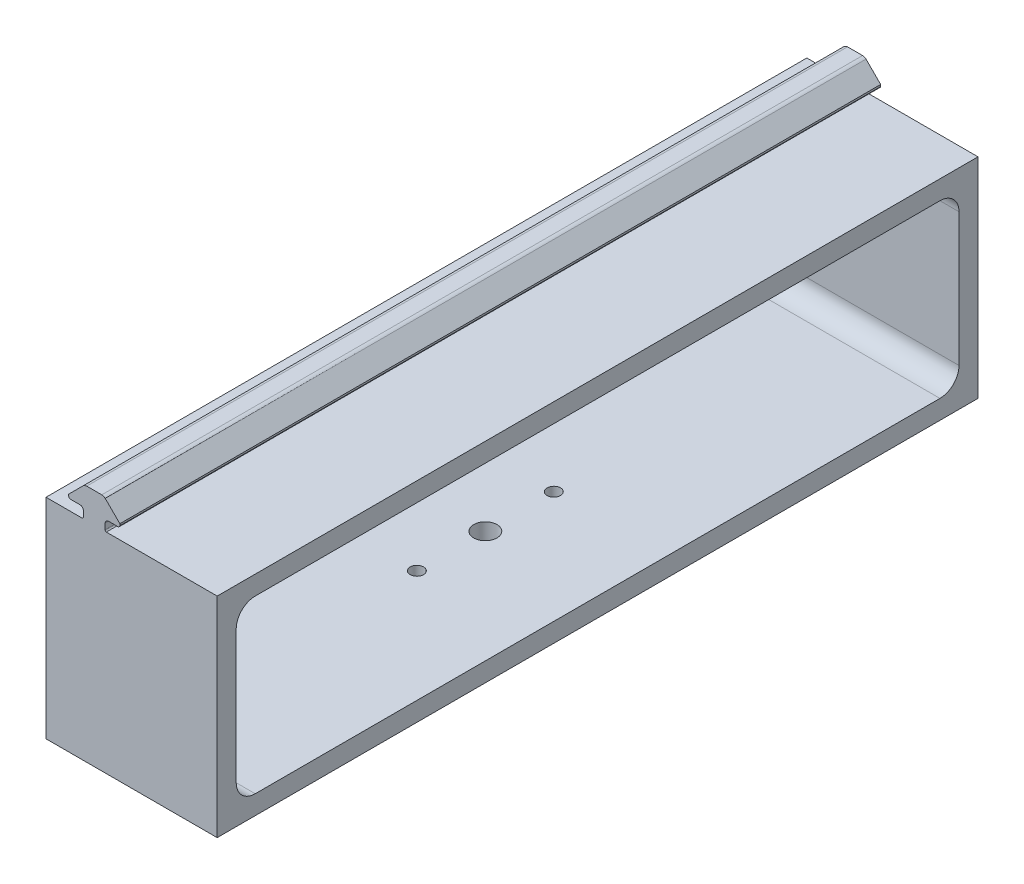
SolidWorks part; units mm, degrees
ref_plane "Front Plane" through (0, 0, 0) normal (0, 0, 1) x (1, 0, 0)
ref_plane "Top Plane" through (0, 0, 0) normal (0, 1, 0) x (1, 0, 0)
ref_plane "Right Plane" through (0, 0, 0) normal (1, 0, 0) x (0, 0, -1)
sketch "body sketch" plane through (0, 0, 0) normal (0, 0, 1) x (1, 0, 0)
  line L0 (-9.8141, 31.5907) -> (-9.8141, 23.3992) construction
  line L1 (-11.7928, 31.2966) -> (-7.8354, 31.2966)
  line L2 (-6.9378, 30.9425) -> (-3.0834, 27.088)
  line L3 (-3.0834, 27.088) -> (-3.0834, 26.6272)
  line L4 (-3.5442, 26.1664) -> (-6.0939, 26.1664)
  line L5 (-6.9378, 25.3225) -> (-6.9378, 23.7712)
  line L6 (-12.6904, 25.3225) -> (-12.6904, 23.7712)
  line L7 (-16.084, 26.1664) -> (-13.5343, 26.1664)
  line L8 (-16.5448, 27.088) -> (-16.5448, 26.6272)
  line L9 (-12.6904, 30.9425) -> (-16.5448, 27.088)
  line L10 (-12.9824, 23.4093) -> (-22.5, 23.4093)
  line L11 (-22.5, 23.4093) -> (-22.5, -31.5907)
  line L12 (-22.5, -31.5907) -> (22.5, -31.5907)
  line L13 (22.5, -31.5907) -> (22.5, 23.4093)
  line L14 (22.5, 23.4093) -> (-6.6458, 23.4093)
  arc A0 (-6.0939, 26.1664) -> (-6.9378, 25.3225) centre (-6.0704, 25.299) ccw
  arc A1 (-3.5442, 26.1664) -> (-3.0834, 26.6272) centre (-3.6789, 26.7619) ccw
  arc A2 (-6.9378, 23.7712) -> (-6.6458, 23.4093) centre (-6.5587, 23.7784) ccw
  arc A3 (-7.8354, 31.2966) -> (-6.9378, 30.9425) centre (-8.1959, 29.0683) cw
  arc A4 (-12.6904, 23.7712) -> (-12.9824, 23.4093) centre (-13.0695, 23.7784) cw
  arc A5 (-13.5343, 26.1664) -> (-12.6904, 25.3225) centre (-13.5578, 25.299) cw
  arc A6 (-16.084, 26.1664) -> (-16.5448, 26.6272) centre (-15.9493, 26.7619) cw
  arc A7 (-11.7928, 31.2966) -> (-12.6904, 30.9425) centre (-11.4323, 29.0683) ccw
  point P5 (-9.8141, 31.2966)
  point P32 (-9.8141, 31.2966)
extrude "Boss-Extrude1" add sketch "body sketch" along normal blind 200
sketch "body cut" plane through (22.5, 0, 0) normal (1, 0, 0) x (0, 0, -1)
  line L0 (-100, 23.4093) -> (-100, -31.5907) construction
  line L1 (-200, 23.4093) -> (0, 23.4093) construction
  line L2 (-200, -31.5907) -> (0, -31.5907) construction
  line L3 (-200, -4.0907) -> (0, -4.0907) construction
  line L4 (-200, -31.5907) -> (-200, 23.4093) construction
  line L5 (0, -31.5907) -> (0, 23.4093) construction
  line L7 (-195, -26.5907) -> (-5, -26.5907)
  line L8 (-195, -26.5907) -> (-195, 18.4093)
  line L9 (-195, 18.4093) -> (-5, 18.4093)
  line L10 (-5, -26.5907) -> (-5, 18.4093)
  line L11 (-195, -26.5907) -> (-5, 18.4093) construction
  line L12 (-195, 18.4093) -> (-5, -26.5907) construction
  point P12 (-100, -4.0907)
  dimension "D1" = 190
  dimension "D2" = 45
extrude "main body hole" cut sketch "body cut" against normal through all both and the other way through all
sketch "screw holes" plane through (0, -31.5907, 0) normal (0, -1, 0) x (-1, 0, 0)
  line L0 (-23.3392, -100) -> (13.9588, -100) construction
  line L1 (22.5, -100) -> (-38.9995, -100) construction
  line L2 (22.5, -200) -> (22.5, 0) construction
  line L3 (-22.5, -200) -> (-22.5, 0) construction
  line L4 (22.5, 0) -> (-22.5, 0) construction
  circle A0 centre (7.01, -100) radius 3.0578
  circle A1 centre (7.01, -81.9999) radius 1.7645
  circle A2 centre (7.01, -117.9999) radius 1.7645
  dimension "D8" = 3.529
  dimension "D9" = 6.1156
  dimension "D10" = 3.529
  dimension "D1" = 18.0001
  dimension "D2" = 17.9999
  dimension "D3" = 0
  dimension "D4" = 15.49
  dimension "D5" = 0
  dimension "D6" = 15.49
  dimension "D7" = 15.49
extrude "hole cuts" cut sketch "screw holes" against normal blind 10
fillet "Fillet1" radius 5 4 edges at (0, -26.5907, 195) (0, 18.4093, 195) (0, 18.4093, 5) (0, -26.5907, 5)
